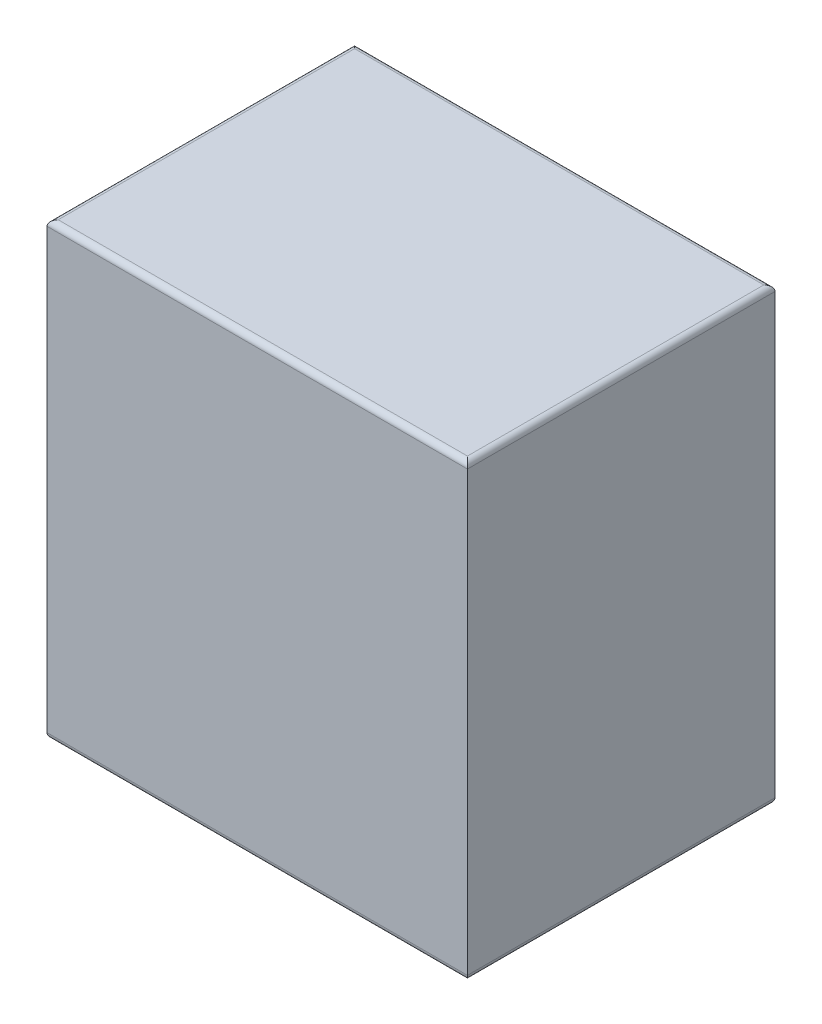
SolidWorks part; units mm, degrees
ref_plane "Front Plane" through (0, 0, 0) normal (0, 0, 1) x (1, 0, 0)
ref_plane "Top Plane" through (0, 0, 0) normal (0, 1, 0) x (1, 0, 0)
ref_plane "Right Plane" through (0, 0, 0) normal (1, 0, 0) x (0, 0, -1)
sketch "Sketch1" plane through (0, 0, 0) normal (0, 1, 0) x (1, 0, 0)
  line L1 (0, 0) -> (37.4, 0)
  line L2 (0, 0) -> (0, 27.36)
  line L3 (0, 27.36) -> (37.4, 27.36)
  line L4 (37.4, 0) -> (37.4, 27.36)
  dimension "D1" = 37.4
  dimension "D2" = 27.36
extrude "Boss-Extrude1" add sketch "Sketch1" along normal blind 40
fillet "Fillet1" radius 0.5 8 edges at (18.7, 0, 0) (37.4, 0, -13.68) (18.7, 0, -27.36) (0, 0, -13.68) (18.7, 40, -27.36) (37.4, 40, -13.68) (18.7, 40, 0) (0, 40, -13.68)
